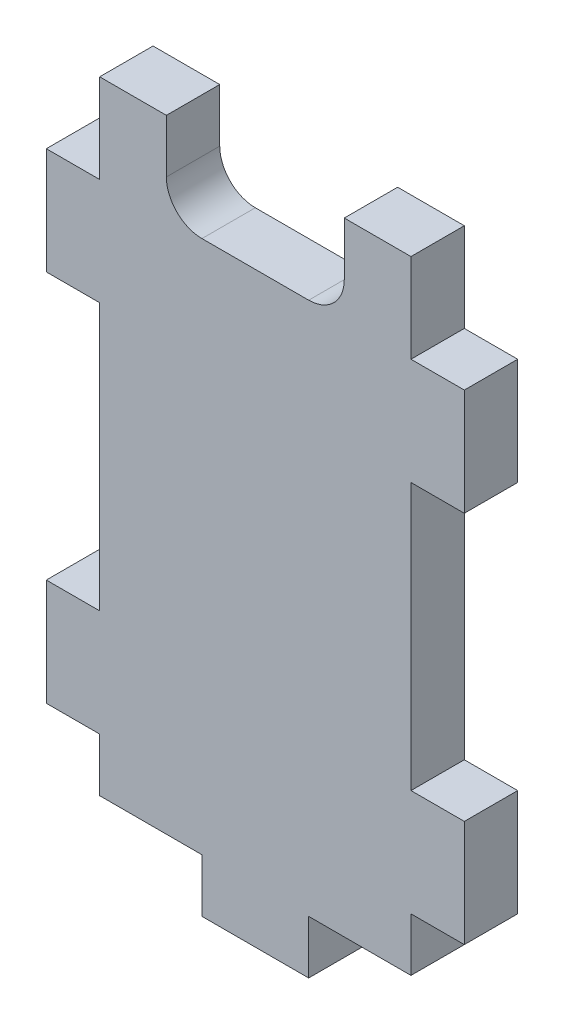
SolidWorks part; units mm, degrees
ref_plane "Front Plane" through (0, 0, 0) normal (0, 0, 1) x (1, 0, 0)
ref_plane "Top Plane" through (0, 0, 0) normal (0, 1, 0) x (1, 0, 0)
ref_plane "Right Plane" through (0, 0, 0) normal (1, 0, 0) x (0, 0, -1)
sketch "Sketch2" plane through (0, 0, 0) normal (0, 1, 0) x (1, 0, 0)
  line L0 (0, 0) -> (0, 6) construction
  dimension "D1" = 6
sketch "Sketch1" plane through (0, 0, 0) normal (0, 0, 1) x (1, 0, 0)
  line L0 (0, -35) -> (0, -41)
  line L1 (-17.5, -35) -> (17.5, -35)
  line L2 (-17.5, -35) -> (-17.5, 35)
  line L3 (-17.5, 35) -> (17.5, 35)
  line L4 (17.5, -35) -> (17.5, 35)
  line L5 (-17.5, -35) -> (17.5, 35)
  line L6 (-17.5, 35) -> (17.5, -35)
  line L7 (0, -41) -> (-6, -41)
  line L8 (-6, -41) -> (-6, -35)
  line L9 (-6, -35) -> (6, -35)
  line L10 (6, -35) -> (6, -41)
  line L11 (6, -41) -> (0, -41)
  line L12 (23.5, -29) -> (23.5, -35) construction
  line L13 (17.5, 25) -> (23.5, 25)
  line L14 (17.5, 25) -> (17.5, 13)
  line L15 (17.5, 13) -> (23.5, 13)
  line L16 (23.5, 25) -> (23.5, 13)
  line L17 (17.5, -17) -> (23.5, -17)
  line L18 (17.5, -17) -> (17.5, -29)
  line L19 (17.5, -29) -> (23.5, -29)
  line L20 (23.5, -17) -> (23.5, -29)
  line L22 (23.5, -35) -> (17.5, -35) construction
  line L23 (10, 35) -> (10, 25)
  line L24 (10, 25) -> (-10, 25)
  line L25 (-10, 25) -> (-10, 35)
  line L26 (0, 25) -> (0, 35) construction
  line L27 (17.5, 25) -> (10, 25) construction
  point P0 (0, 0)
  dimension "D1" = 70
  dimension "D2" = 35
  dimension "D3" = 6
  dimension "D4" = 12
  dimension "D5" = 12
  dimension "D6" = 10
  dimension "D7" = 20
extrude "Boss-Extrude1" add sketch "Sketch1" against normal up to vertex (6 mm away) contours L6 L2 L5 | L24 L25 L3 L6 L5 L23 | L5 L6 L4 | L6 L5 L1 | L11 L10 L1 L0 | L8 L7 L0 L1 region at (3, -38, 0) region at (-3, -38, 0) region at (0, -23.3333, 0) region at (-11.6667, 0, 0) region at (11.6667, 0, 0) region at (0, 20.101, 0) up to point (0, 0, -6)
extrude "Boss-Extrude2" add sketch "Sketch1<3>" against normal up to surface (6 mm away) contours L16 L13 L4 L15 | L20 L17 L4 L19 region at (20.5, -23, 0) region at (20.5, 19, 0) up to face at (0, -2.6667, -6)
sketch "Sketch1<3>" plane through (0, 0, 0) normal (0, 0, 1) x (1, 0, 0) same geometry as "Sketch1"
mirror "Mirror1" about plane through (0, 0, 0) normal (1, 0, 0) of "Boss-Extrude2"
fillet "Fillet2" radius 4 2 edges at (-10, 25, -3) (10, 25, -3)
equation "\"t_wood\"= 6' Thickness of the wood"
equation "\"t_glass\"= 2.5'Thickness of glass panels"
equation "\"w_glass\"= 181"
equation "\"h_glass\"= 151"
equation "\"h_food_internal\" = 60"
equation "\"entry_height\"= 20"
equation "\"entry diameter\"= 8"
equation "\"glass_bottom_overlap\"= 8"
equation "\"default_finger_size\"= 12"
equation "\"brood_depth\"= 42"
equation "\"outer_box_depth\" = \"brood_depth\" + ( 2 * \"t_glass\" ) + ( 2 * \"t_wood\" )"
equation "\"outer_box_width\"= \"w_glass\" + ( 2 * \"t_wood\" )"
equation "\"food_top_clearance\"= 10"
equation "\"outer_box_height\"= \"t_wood\" + \"h_glass\" + \"t_wood\" + \"h_food_internal\" + \"food_top_clearance\" + \"t_wood\""
equation "\"food_internal_depth\"= \"brood_depth\" + \"t_glass\" + \"t_glass\" - \"t_wood\" - \"t_wood\""
equation "\"food_channel_clearance_width\"= 14"
equation "\"bar_top_play\"= 0.5"
equation "\"bar_entry_angle\"= 10"
equation "\"bar_width\"= 20"
equation "\"entry_disk_play\"= 0.3"
equation "\"D1@Sketch2\"=\"t_wood\""
equation "\"D1@Sketch1\"=\"food_top_clearance\"+\"h_food_internal\""
equation "\"D2@Sketch1\"=\"food_internal_depth\""
equation "\"D3@Sketch1\"=\"t_wood\""
equation "\"D4@Sketch1\"=\"default_finger_size\""
equation "\"D5@Sketch1\"=\"default_finger_size\""
equation "\"D6@Sketch1\"=\"food_top_clearance\""
equation "\"D7@Sketch1\"=\"bar_width\""
